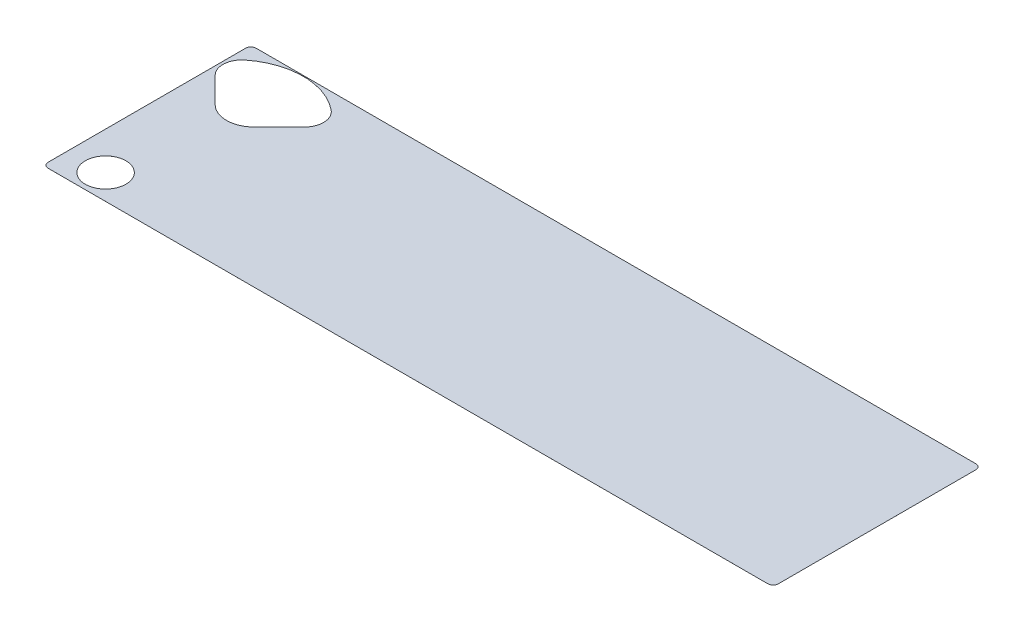
SolidWorks part; units mm, degrees
note: '?' marks a value the reader was unsure of.
material "PET"
ref_plane "Front Plane" through (0, 0, 0) normal (0, 0, 1) x (1, 0, 0)
ref_plane "Top Plane" through (0, 0, 0) normal (0, 1, 0) x (1, 0, 0)
ref_plane "Right Plane" through (0, 0, 0) normal (1, 0, 0) x (0, 0, -1)
ref_axis "Axis1" through (0, -55, 0) along (0, 1, 0)?
sketch "Sketch2" plane through (0, 0, 0) normal (0, 1, 0) x (1, 0, 0)
  line L0 (-841.2096, -227.3383) -> (-841.2096, 227.3383) construction
  line L1 (-828.9373, 239.6106) -> (828.9373, 239.6106) construction
  line L2 (841.2096, 227.3383) -> (841.2096, -227.3383) construction
  line L3 (828.9373, -239.6106) -> (-828.9373, -239.6106) construction
  line L4 (-841.2096, -227.3383) -> (-841.2096, 227.3383)
  line L5 (-828.9373, 239.6106) -> (828.9373, 239.6106)
  line L6 (841.2096, 227.3383) -> (841.2096, -227.3383)
  line L7 (828.9373, -239.6106) -> (-828.9373, -239.6106)
  line L10 (-822.2491, 138.2967) -> (-763.8611, 79.9087)
  line L11 (-674.2746, 79.9087) -> (-615.8867, 138.2967)
  line L12 (-822.2491, 138.2967) -> (-763.8611, 79.9087)
  line L13 (-674.2746, 79.9087) -> (-615.8867, 138.2967)
  circle A1 centre (-754.5064, -181.8446) radius 46.83
  circle A2 centre (-754.5064, -181.8446) radius 46.83
  arc A6 (-763.8611, 79.9087) -> (-674.2746, 79.9087) centre (-719.0679, 124.7019) ccw
  arc A7 (-615.8867, 138.2967) -> (-619.376, 202.7297) centre (-646.5378, 168.9478) ccw
  arc A8 (-619.376, 202.7297) -> (-818.7598, 202.7297) centre (-719.0679, 78.74) ccw
  arc A9 (-818.7598, 202.7297) -> (-822.2491, 138.2967) centre (-791.598, 168.9478) ccw
  arc A10 (-763.8611, 79.9087) -> (-674.2746, 79.9087) centre (-719.0679, 124.7019) ccw
  arc A11 (-615.8867, 138.2967) -> (-619.376, 202.7297) centre (-646.5378, 168.9478) ccw
  arc A12 (-619.376, 202.7297) -> (-818.7598, 202.7297) centre (-719.0679, 78.74) ccw
  arc A13 (-818.7598, 202.7297) -> (-822.2491, 138.2967) centre (-791.598, 168.9478) ccw
  spline S0 degree 3 poles (-3631.319, 806.7985) (-650.9044, -50.011) (-797.9032, -262.9307) (-837.8611, -236.2621) (-864.5297, -196.3043) (-651.6105, -49.3058) (205.1963, -3029.7089) knots -10.956161 -10.956161 -10.956161 -10.956161 -0.38516 0 0.38516 10.956147 10.956147 10.956147 10.956147 only from (-828.9373, -239.6106) to (-841.2096, -227.3383) construction
  spline S1 degree 3 poles (205.1995, 3029.72) (-651.61, 49.3054) (-864.5297, 196.3042) (-837.8611, 236.2621) (-797.9033, 262.9307) (-650.9048, 50.0115) (-3631.3079, -806.7953) knots -10.956161 -10.956161 -10.956161 -10.956161 -0.38516 0 0.38516 10.956147 10.956147 10.956147 10.956147 only from (-841.2096, 227.3383) to (-828.9373, 239.6106) construction
  spline S2 degree 3 poles (3631.319, -806.7985) (650.9044, 50.011) (797.9032, 262.9307) (837.8611, 236.2621) (864.5297, 196.3043) (651.6105, 49.3058) (-205.1963, 3029.7089) knots -10.956161 -10.956161 -10.956161 -10.956161 -0.38516 0 0.38516 10.956147 10.956147 10.956147 10.956147 only from (828.9373, 239.6106) to (841.2096, 227.3383) construction
  spline S3 degree 3 poles (-205.1995, -3029.72) (651.61, -49.3054) (864.5297, -196.3042) (837.8611, -236.2621) (797.9033, -262.9307) (650.9048, -50.0115) (3631.3079, 806.7953) knots -10.956161 -10.956161 -10.956161 -10.956161 -0.38516 0 0.38516 10.956147 10.956147 10.956147 10.956147 only from (841.2096, -227.3383) to (828.9373, -239.6106) construction
  spline S4 degree 3 poles (-828.9373, -239.6106) (-830.5403, -239.6106) (-833.7901, -238.9792) (-837.8611, -236.2621) (-840.5782, -232.1911) (-841.2096, -228.9413) (-841.2096, -227.3383) knots -0.770319 -0.770319 -0.770319 -0.770319 -0.38516 0 0.38516 0.770319 0.770319 0.770319 0.770319
  spline S5 degree 3 poles (-841.2096, 227.3383) (-841.2096, 228.9413) (-840.5782, 232.1911) (-837.8611, 236.2621) (-833.7901, 238.9792) (-830.5403, 239.6106) (-828.9373, 239.6106) knots -0.770319 -0.770319 -0.770319 -0.770319 -0.38516 0 0.38516 0.770319 0.770319 0.770319 0.770319
  spline S6 degree 3 poles (828.9373, 239.6106) (830.5403, 239.6106) (833.7901, 238.9792) (837.8611, 236.2621) (840.5782, 232.1911) (841.2096, 228.9413) (841.2096, 227.3383) knots -0.770319 -0.770319 -0.770319 -0.770319 -0.38516 0 0.38516 0.770319 0.770319 0.770319 0.770319
  spline S7 degree 3 poles (841.2096, -227.3383) (841.2096, -228.9413) (840.5782, -232.1911) (837.8611, -236.2621) (833.7901, -238.9792) (830.5403, -239.6106) (828.9373, -239.6106) knots -0.770319 -0.770319 -0.770319 -0.770319 -0.38516 0 0.38516 0.770319 0.770319 0.770319 0.770319
  dimension "D1" = 0
  dimension "D2" = 0
extrude "Boss-Extrude1" add sketch "Sketch2" along normal blind 0.005 from surface
